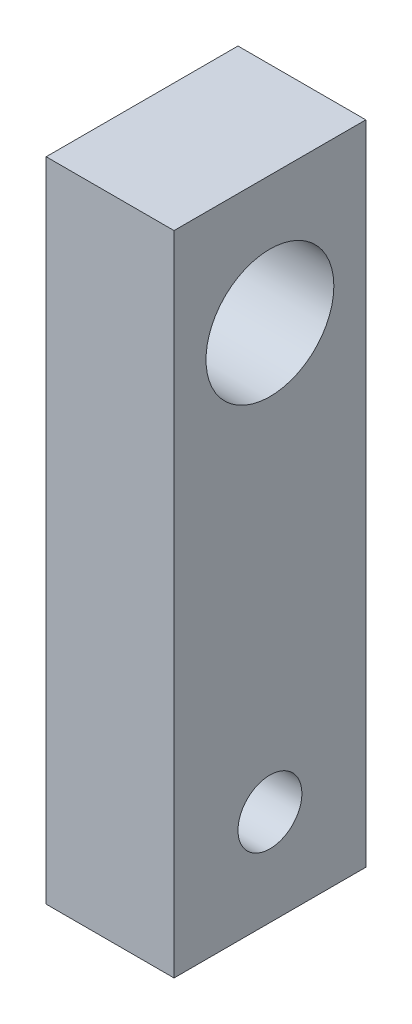
SolidWorks part; units mm, degrees
ref_plane "Front Plane" through (0, 0, 0) normal (0, 0, 1) x (1, 0, 0)
ref_plane "Top Plane" through (0, 0, 0) normal (0, 1, 0) x (1, 0, 0)
ref_plane "Right Plane" through (0, 0, 0) normal (1, 0, 0) x (0, 0, -1)
sketch "Sketch5" plane through (0, 0, 0) normal (1, 0, 0) x (0, 0, -1)
  line L0 (3, 0) -> (3, 3) construction
  line L1 (0, 0) -> (6, 0)
  line L2 (0, 0) -> (0, 20.25)
  line L3 (0, 20.25) -> (6, 20.25)
  line L4 (6, 0) -> (6, 20.25)
  line L5 (3, 3) -> (3, 10) construction
  line L6 (3, 10) -> (3, 11) construction
  line L7 (3, 11) -> (3, 16.25) construction
  line L8 (3, 16.25) -> (3, 20.25) construction
  circle A0 centre (3, 3) radius 1
  circle A1 centre (3, 16.25) radius 2
  dimension "D7" = 4
  dimension "D8" = 2
  dimension "D1" = 6
  dimension "D2" = 3
  dimension "D3" = 10
  dimension "D4" = 4
  dimension "D5" = 5.25
  dimension "D6" = 1
extrude "Boss-Extrude2" add sketch "Sketch5" along normal blind 4
equation "\"post_length\"=6"
equation "\"post_width\" = 4"
equation "\"post_height\"=13"
equation "\"pin_offset\" = 3"
equation "\"pin_dia\"=2"
equation "\"pin_dist_from_top\"=4"
equation "\"D1@Sketch5\"= \"post_length\""
equation "\"D2@Sketch5\"=\"pin_offset\""
equation "\"pin_depth\"= 10"
equation "\"D3@Sketch5\"=\"pin_depth\""
equation "\"D4@Sketch5\"=\"pin_dist_from_top\""
equation "\"pin_bearing_OD\"= 10.5"
equation "\"D5@Sketch5\"=\"pin_bearing_OD\"/2"
equation "\"post_clearance\"=1"
equation "\"D6@Sketch5\"=\"post_clearance\""
equation "\"bearing_pin_dia\"=4"
equation "\"D7@Sketch5\"=\"bearing_pin_dia\""
equation "\"D8@Sketch5\"=\"pin_dia\""
equation "\"D1@Boss-Extrude2\"=\"post_width\""
